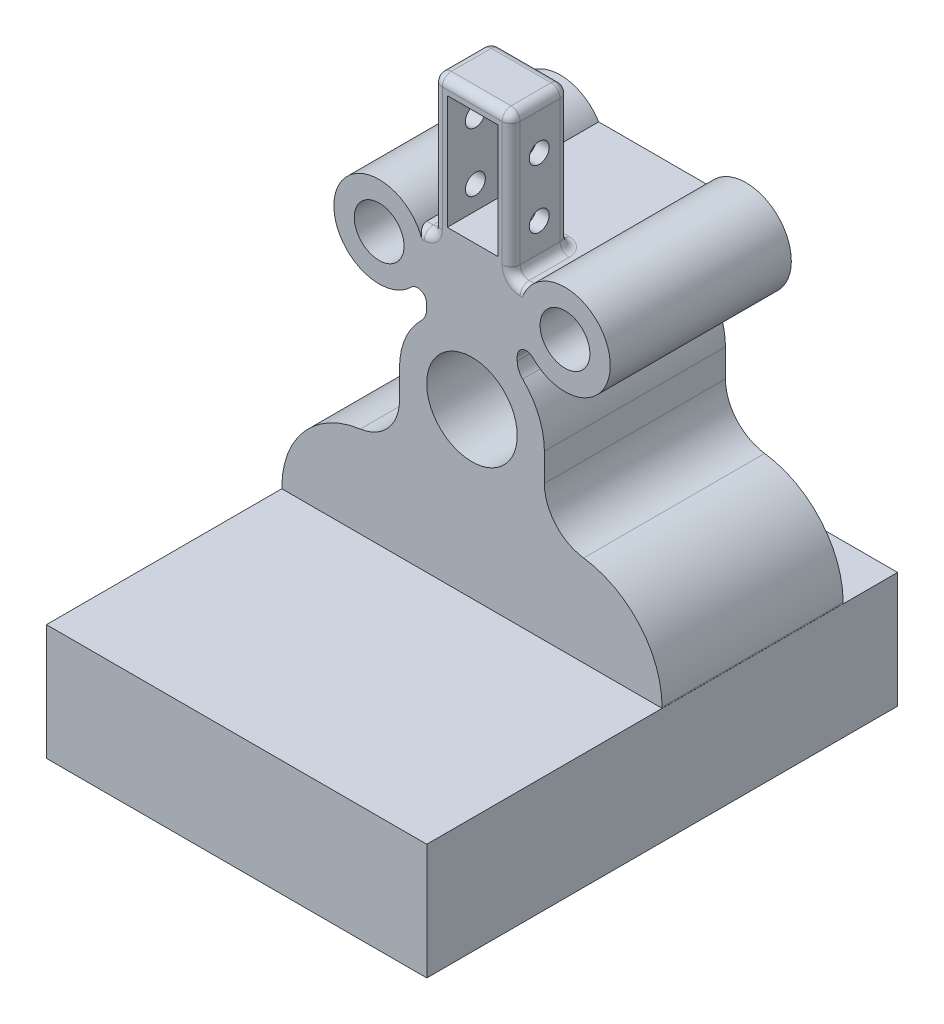
SolidWorks part; units mm, degrees
ref_plane "Alzado" through (0, 0, 0) normal (0, 0, 1) x (1, 0, 0)
ref_plane "Planta" through (0, 0, 0) normal (0, 1, 0) x (1, 0, 0)
ref_plane "Vista lateral" through (0, 0, 0) normal (1, 0, 0) x (0, 0, -1)
sketch "Croquis1" plane through (0, 0, 0) normal (0, 0, 1) x (1, 0, 0)
  line L0 (-5.0259, -5.2675) -> (-5.0259, -8.2675)
  line L1 (4.9741, -8.2675) -> (4.9741, -5.2675)
  line L2 (-8.0259, -14.5125) -> (7.9741, -14.5125) construction
  line L3 (-5.0259, -5.2675) -> (-6.0259, -5.2675)
  line L4 (-6.0259, 0) -> (-5.0259, 0)
  line L5 (6.0259, 0) -> (5.0259, 0)
  line L6 (4.9741, -5.2675) -> (5.9741, -5.2675)
  line L7 (-5.0259, 0) -> (5.0259, 0)
  arc A0 (-5.0259, -8.2675) -> (4.9741, -8.2675) centre (-0.0259, -14.5125) ccw
  circle A1 centre (-0.0259, -14.5125) radius 5
  arc A2 (-6.0259, 0) -> (-6.0259, -5.2675) centre (-10.276, -2.6338) ccw
  circle A3 centre (-10.276, -2.6338) radius 2.75
  arc A4 (6.0259, 0) -> (5.9741, -5.2675) centre (10.2498, -2.6756) cw
  circle A5 centre (10.2498, -2.6756) radius 2.75
  point P18 (0, 0)
  dimension "D1" = 10
  dimension "D5" = 5.5
  dimension "D3" = 3
  dimension "D4" = 1
extrude "Saliente-Extruir1" add sketch "Croquis1" along normal blind 20
ref_plane "Plano1" through (0, 0, 10) normal (0, 0, -1) x (-1, 0, 0)
sketch "Croquis5" plane through (0, 0, 10) normal (0, 0, -1) x (-1, 0, 0)
  line L0 (0.0259, -14.5125) -> (0.0259, -32.5925) construction
  line L1 (-7.9741, -14.5125) -> (-7.9741, -32.5925)
  line L2 (-7.9741, -32.5925) -> (8.0259, -32.5925)
  line L3 (8.0259, -32.5925) -> (8.0259, -14.5125)
  arc A0 (-4.9741, -8.2675) -> (5.0259, -8.2675) centre (0.0259, -14.5125) ccw construction
  arc A1 (8.0259, -14.5125) -> (-7.9741, -14.5125) centre (0.0259, -14.5125) cw
  dimension "D1" = 18.08
extrude "Saliente-Extruir4" add sketch "Croquis5" along normal mid plane 20
sketch "Croquis7" plane through (0, 0, 20) normal (0, 0, 1) x (1, 0, 0)
  line L0 (20.9741, -32.5925) -> (-21.0259, -32.5925)
  line L2 (7.9741, -32.5925) -> (-8.0259, -32.5925) construction
  point P3 (-0.0259, -32.5925)
  point P6 (-0.0259, -32.5925)
  dimension "D1" = 42
extrude "Extruir-Lámina1" add sketch "Croquis7" against normal blind 20 thin thin type one direction wall 10
sketch "Croquis8" plane through (0, 0, 20) normal (0, 0, 1) x (1, 0, 0)
  line L0 (-0.0259, -14.5125) -> (-0.0259, -32.5925) construction
  line L5 (20.9741, -32.5925) -> (-21.0259, -32.5925) construction
  line L7 (-21.0259, -32.5925) -> (20.9855, -32.5925)
  line L8 (-21.0259, -32.5925) -> (-21.0259, -45.386)
  line L9 (-21.0259, -45.386) -> (20.9855, -45.386)
  line L10 (20.9855, -32.5925) -> (20.9855, -45.386)
extrude "Saliente-Extruir6" add sketch "Croquis8" against normal mid plane 52
fillet "Redondeo1" radius 2 4 edges at (-5.0259, -8.2675, 10) (4.9741, -8.2675, 10) (-5.0259, -5.2675, 10) (4.9741, -5.2675, 10)
fillet "Redondeo2" radius 1 2 edges at (5.9741, -5.2675, 10) (-6.0259, -5.2675, 10)
sketch "Croquis9" plane through (0, 0, 20) normal (0, 0, 1) x (1, 0, 0)
  line L0 (6.0259, 0) -> (-6.0259, 0) construction
  line L1 (4.3, 0) -> (-4.3, 0)
  line L2 (4.3, 0) -> (4.3, 15.7)
  line L3 (4.3, 15.7) -> (-4.3, 15.7)
  line L4 (-4.3, 0) -> (-4.3, 15.7)
  line L5 (-6.0259, 0) -> (6.0259, 0) construction
  line L7 (-2.75, 14.15) -> (2.85, 14.15)
  line L8 (-2.75, 14.15) -> (-2.75, 1.55)
  line L9 (-2.75, 1.55) -> (2.85, 1.55)
  line L10 (2.85, 14.15) -> (2.85, 1.55)
  point P10 (0, 0)
  dimension "D1" = 15.7
  dimension "D2" = 8.6
  dimension "D3" = 12.6
  dimension "D4" = 5.6
  dimension "D5" = 1.55
  dimension "D6" = 1.55
extrude "Saliente-Extruir7" add sketch "Croquis9" against normal blind 6.4
sketch "Croquis11" plane through (4.3, 0, 0) normal (1, 0, 0) x (0, 0, -1)
  line L0 (-13.6, 14.15) -> (-20, 14.15) construction
  circle A0 centre (-16.8993, 10.65) radius 1.1
  circle A1 centre (-16.8993, 4.15) radius 1.1
  dimension "D1" = 6.5
  dimension "D2" = 2.2
  dimension "D3" = 2.2
  dimension "D4" = 3.5
extrude "Cortar-Extruir1" cut sketch "Croquis11" against normal through all both and the other way through all
fillet "Redondeo3" radius 1 13 edges at (-5.163, 0, 20) (5.163, 0, 20) (-4.3, 0, 16.8) (-4.3, 7.85, 13.6) (-4.3, 15.7, 16.8) (-4.3, 7.85, 20) (4.3, 7.85, 13.6) (4.3, 7.85, 20) (0, 15.7, 20) (0, 15.7, 13.6) (4.3, 15.7, 16.8) (0, 0, 13.6) (4.3, 0, 16.8)
fillet "Redondeo4" radius 5 2 edges at (7.9741, -22.5925, 10) (-8.0259, -22.5925, 10)
fillet "Redondeo5" radius 10 2 edges at (-21.0259, -22.5925, 10) (20.9741, -22.5925, 10)
